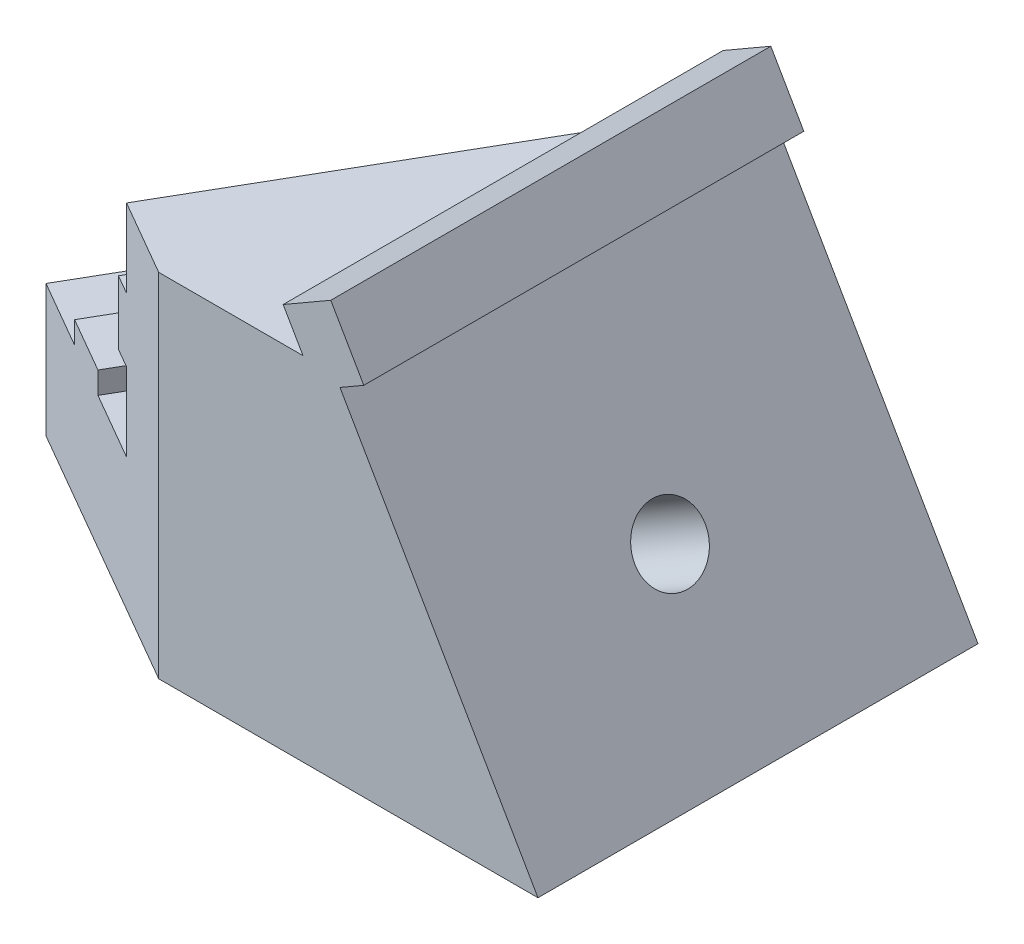
SolidWorks part; units mm, degrees
ref_plane "Front Plane" through (0, 0, 0) normal (0, 0, 1) x (1, 0, 0)
ref_plane "Top Plane" through (0, 0, 0) normal (0, 1, 0) x (1, 0, 0)
ref_plane "Right Plane" through (0, 0, 0) normal (1, 0, 0) x (0, 0, -1)
sketch "Esquisse1" plane through (0, 0, 0) normal (0, 0, 1) x (1, 0, 0)
  line L0 (8, 16) -> (17.2376, 0)
  line L1 (17.2376, 0) -> (0, 0)
  line L2 (0, 0) -> (0, 16)
  line L3 (0, 16) -> (8, 16)
  dimension "D1" = 8
  dimension "D2" = 120
  dimension "D3" = 16
extrude "Boss.-Extru.1" add sketch "Esquisse1" along normal blind 20
sketch "Esquisse2" plane through (12.9282, 7.4641, 0) normal (0.866, 0.5, 0) x (0, 0, -1)
  line L0 (-20, -8.6188) -> (0, -8.6188) construction
  line L3 (-20, -8.6188) -> (-20, 9.8564) construction
  circle A0 centre (-10, -0.6188) radius 1.6
  dimension "D1" = 3.2
  dimension "D2" = 8
  dimension "D3" = 10
extrude "HoleForLauncherFixing" cut sketch "Esquisse2" against normal through all
ref_plane "Plan1" through (8.5981, 4.9641, 0) normal (0.866, 0.5, 0) x (0, 0, -1)
ref_axis "Axe1" through (3.208, 14.3, 0) along (0.5, -0.866, 0)
ref_plane "Plan3" through (0, 0, 0) normal (-0.866, 0, -0.5) x (0, -1, 0)
sketch "Esquisse4" plane through (0, 0, 0) normal (-0.866, 0, -0.5) x (0, -1, 0)
  line L1 (4.4994, 17.8157) -> (-17.7877, 17.8157)
  line L2 (4.4994, 17.8157) -> (4.4994, -17.0003)
  line L3 (4.4994, -17.0003) -> (-17.7877, -17.0003)
  line L4 (-17.7877, 17.8157) -> (-17.7877, -17.0003)
extrude "Enlèv. mat.-Extru.3" cut sketch "Esquisse4" against normal blind 6
ref_plane "Plan4" through (1.7321, 0, -3) normal (-0.5, 0, 0.866) x (0, 1, 0)
ref_plane "Plan5" through (0, 0, 12) normal (0.5, 0, -0.866) x (-0.866, 0, -0.5)
ref_plane "Plan6" through (-8.6603, 0, 15) normal (0.5, 0, -0.866) x (-0.866, 0, -0.5)
sketch "Esquisse5" plane through (-3.4641, 0, 18) normal (0.5, 0, -0.866) x (-0.866, 0, -0.5)
  line L0 (-4, 0) -> (10, 0)
  line L1 (10, 0) -> (10, 6)
  line L2 (10, 6) -> (6.45, 6)
  line L3 (6.45, 6) -> (6.45, 7)
  line L4 (6.45, 7) -> (3.55, 7)
  line L5 (3.55, 7) -> (3.55, 6)
  line L6 (3.55, 6) -> (0, 6)
  line L7 (0, 6) -> (0, 9.55)
  line L8 (0, 9.55) -> (1, 9.55)
  line L9 (1, 9.55) -> (1, 12.45)
  line L10 (1, 12.45) -> (0, 12.45)
  line L11 (0, 12.45) -> (0, 16)
  line L12 (0, 16) -> (-4, 16)
  line L13 (-4, 16) -> (-4, 0)
  point P4 (-5, 0.1996)
  point P7 (-5, 0)
  point P16 (-4, 16)
  dimension "D1" = 10
  dimension "D2" = 2.9
  dimension "D3" = 1
  dimension "D4" = 6
  dimension "D5" = 4
  dimension "D6" = 10
extrude "MakerBeanFixing" add sketch "Esquisse5" along normal blind 21
sketch "Esquisse6" plane through (12.9282, 7.4641, 0) normal (0.866, 0.5, 0) x (0, 0, -1)
  line L0 (0, -8.6188) -> (0, 9.8564) construction
  line L1 (0, 9.3812) -> (-20, 9.3812)
  line L2 (0, 9.3812) -> (0, 12.3812)
  line L3 (0, 12.3812) -> (-20, 12.3812)
  line L4 (-20, 9.3812) -> (-20, 12.3812)
  line L5 (-20, -8.6188) -> (0, -8.6188) construction
  point P9 (0, 0)
  dimension "D1" = 18
  dimension "D2" = 3
extrude "AntiRotationSystem" add sketch "Esquisse6" along normal mid plane 2.5
sketch "Esquisse7" plane through (0, 7, 0) normal (0, 1, 0) x (1, 0, 0)
  line L2 (1.45, 3.4115) -> (3.9615, 1.9615) construction
  line L3 (3.9615, 1.9615) -> (-6.5385, -16.225) construction
  circle A0 centre (0.2058, -1.6436) radius 1.6
  dimension "D1" = 3.2
  dimension "D2" = 5
  dimension "D3" = 1.45
extrude "TopMakerBeanFixingHole" cut sketch "Esquisse7" against normal through all
sketch "Esquisse8" plane through (0, 0, 0) normal (0, 0, -1) x (-1, 0, 0)
  line L0 (-8.2376, 15.5885) -> (-17.2376, 0)
  line L1 (-17.2376, 0) -> (-8.2376, 15.5885) construction
  line L2 (-17.2376, 0) -> (-20.9182, 2.125)
  line L3 (-20.9182, 2.125) -> (-10.4182, 20.3115)
  line L4 (-8.2376, 15.5885) -> (-9.3201, 16.2135)
  line L6 (-17.2376, 0) -> (-8.2376, 15.5885) construction
  line L9 (-9.3201, 16.2135) -> (-7.8201, 18.8115)
  line L10 (-7.8201, 18.8115) -> (-10.4182, 20.3115)
  dimension "D1" = 3
extrude "Enlèv. mat.-Extru.4" cut sketch "Esquisse8" against normal through all
sketch "Esquisse3" plane through (8.5981, 4.9641, 0) normal (0.866, 0.5, 0) x (0, 0, -1)
  circle A0 centre (-10, -0.6188) radius 4.25
  circle A1 centre (-10, -0.6188) radius 1.6 construction
  dimension "D1" = 8.5
extrude "BigHoleForLauncherFixing" cut sketch "Esquisse3" against normal through all
